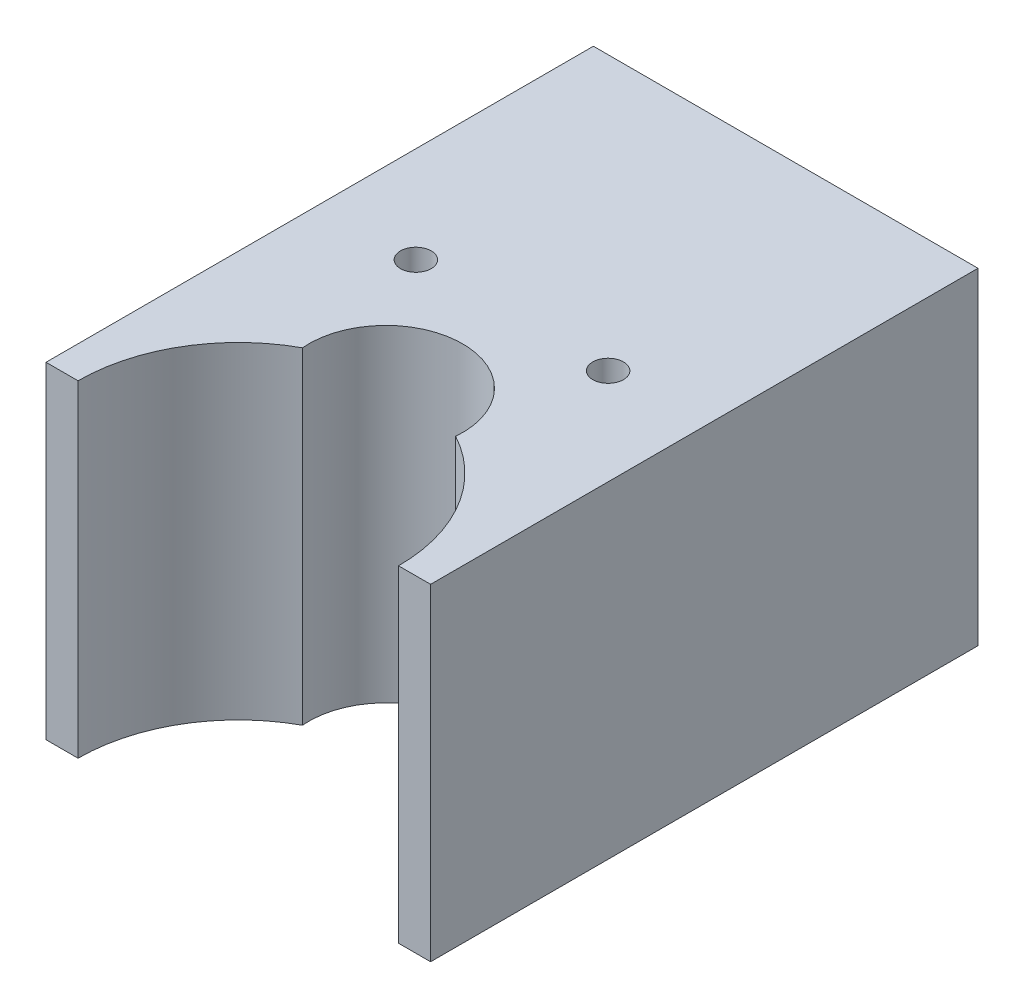
SolidWorks part; units mm, degrees
ref_plane "前视基准面" through (0, 0, 0) normal (0, 0, 1) x (1, 0, 0)
ref_plane "上视基准面" through (0, 0, 0) normal (0, 1, 0) x (1, 0, 0)
ref_plane "右视基准面" through (0, 0, 0) normal (1, 0, 0) x (0, 0, -1)
other "Configuration Table"
sketch "草图1" plane through (0, 0, 0) normal (0, 1, 0) x (1, 0, 0)
  line L1 (0, 0) -> (15, 0)
  line L2 (0, 0) -> (0, -32.4)
  line L3 (0, -32.4) -> (15, -32.4)
  line L4 (15, 0) -> (15, -32.4)
  circle A4 centre (3, -3) radius 0.8
  circle A5 centre (12, -3) radius 0.8
  circle A6 centre (3, -29.4) radius 0.8
  circle A7 centre (12, -29.4) radius 0.8
  circle A8 centre (7.5, -21.35) radius 6.25
  circle A9 centre (7.5, -15.6) radius 3
  point P10 (7.5, -32.4)
  dimension "D3" = 1.6
  dimension "D6" = 12.5
  dimension "D7" = 6
  dimension "D1" = 3
  dimension "D2" = 15
  dimension "D4" = 11.05
  dimension "D5" = 5.75
  dimension "D9" = 3
  dimension "D10" = 3
  dimension "D11" = 3
  dimension "32.4" = 32.4
extrude "凸台-拉伸1" add sketch "草图1" along normal blind 12.75 contours L2 L3 L4 L1
extrude "切除-拉伸1" cut sketch "草图1<3>" along normal through all contours A9 | A8
sketch "草图1<3>" plane through (0, 0, 0) normal (0, 1, 0) x (1, 0, 0) same geometry as "草图1"
sketch "草图2" plane through (0, 12.75, 0) normal (0, 1, 0) x (1, 0, 0)
  line L0 (0, 0) -> (15, 0) construction
  line L1 (15, 0) -> (0, 0)
  line L2 (15, 0) -> (15, -21.35)
  line L3 (15, -21.35) -> (0, -21.35)
  line L4 (0, 0) -> (0, -21.35)
  line L5 (15, 0) -> (15, -32.4) construction
  line L6 (0, 0) -> (0, -32.4) construction
  line L7 (7.5, -21.35) -> (7.5, -32.4) construction
  line L8 (0, -32.4) -> (15, -32.4) construction
  arc A2 (4.5114, -15.8609) -> (10.4886, -15.8609) centre (7.5, -21.35) ccw construction
  point P14 (0, 0)
extrude "切除-拉伸2" cut sketch "草图2" against normal through all flip side to cut
sketch "草图3" plane through (0, 0, 0) normal (0, -1, 0) x (1, 0, 0)
  circle A0 centre (3.5, 11.35) radius 0.6
  circle A1 centre (11.5, 11.35) radius 0.6
  point P4 (0, 0)
  dimension "D1" = 1.2
extrude "切除-拉伸3" cut sketch "草图3" against normal blind 3
sketch "草图4" plane through (0, 12.75, 0) normal (0, 1, 0) x (1, 0, 0)
  circle A0 centre (11.25, -10.675) radius 0.6
  circle A1 centre (3.75, -10.675) radius 0.6
  point P4 (0, 0)
  dimension "D1" = 1.2
extrude "切除-拉伸4" cut sketch "草图4" against normal blind 3
